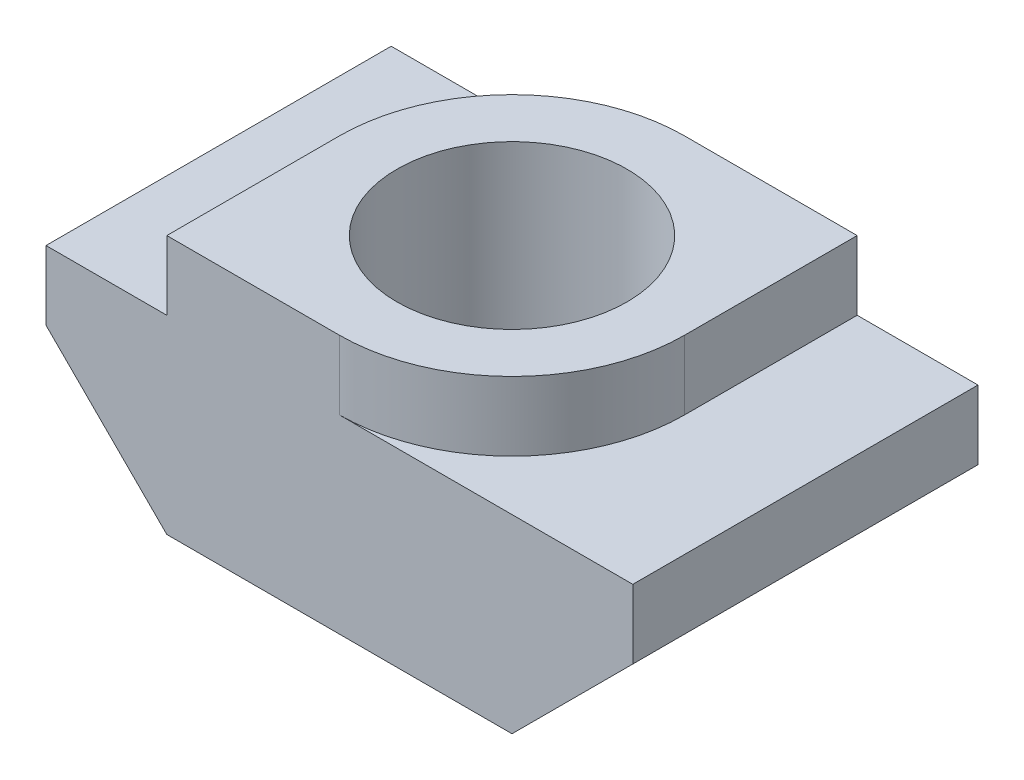
SolidWorks part; units mm, degrees
ref_plane "前视基准面" through (0, 0, 0) normal (0, 0, 1) x (1, 0, 0)
ref_plane "上视基准面" through (0, 0, 0) normal (0, 1, 0) x (1, 0, 0)
ref_plane "右视基准面" through (0, 0, 0) normal (1, 0, 0) x (0, 0, -1)
other "Configuration Table"
sketch "草图1" plane through (0, 0, 0) normal (0, 1, 0) x (1, 0, 0)
  line L1 (0, 0) -> (10.2, 0)
  line L2 (0, 0) -> (0, 6)
  line L3 (0, 6) -> (10.2, 6)
  line L4 (10.2, 0) -> (10.2, 6)
  dimension "D1" = 6
  dimension "D2" = 10.2
extrude "凸台-拉伸1" add sketch "草图1" along normal blind 3.3
sketch "草图2" plane through (0, 0, 0) normal (0, 1, 0) x (1, 0, 0)
  line L0 (10.2, 6) -> (0, 6) construction
  line L1 (2.1, 3) -> (2.1, 0)
  line L2 (0, 0) -> (10.2, 0) construction
  line L3 (2.1, 0) -> (5.1, 0)
  line L4 (5.1, 6) -> (8.1, 6)
  line L5 (8.1, 6) -> (8.1, 3)
  circle A0 centre (5.1, 3) radius 2
  arc A1 (5.1, 0) -> (8.1, 3) centre (5.1, 3) ccw
  arc A2 (5.1, 6) -> (2.1, 3) centre (5.1, 3) ccw
  dimension "D3" = 4
  dimension "D1" = 3
  dimension "D2" = 5.1
extrude "凸台-拉伸2" add sketch "草图2" along normal blind 1.2 from surface contours A1 L5 L4 A2 L1 L3 starting at face at (5.1, 3.3, -3)
sketch "草图3" plane through (0, 0, 0) normal (0, 0, 1) x (1, 0, 0)
  line L0 (0, 2.1) -> (2.1, 0)
  line L1 (0, 3.3) -> (0, 0) construction
  line L2 (0, 0) -> (10.2, 0) construction
  line L3 (2.1, 0) -> (8.1, 0) construction
  line L4 (8.1, 0) -> (10.2, 2.1)
  line L5 (10.2, 3.3) -> (10.2, 0) construction
  line L6 (10.2, 2.1) -> (0, 2.1) construction
  line L7 (0, 3.3) -> (2.1, 3.3) construction
  line L8 (5.1, 9.0744) -> (5.1, -3.0876) construction
  line L9 (0, 2.1) -> (0, 0)
  line L10 (0, 0) -> (2.1, 0)
  line L11 (10.2, 2.1) -> (10.2, 0)
  line L12 (10.2, 0) -> (8.1, 0)
  point P6 (7.8566, 0)
  point P11 (0, 0)
  point P14 (0, 0)
  dimension "D1" = 1.2
  dimension "D2" = 135
extrude "切除-拉伸2" cut sketch "草图3" against normal through all
extrude "切除-拉伸4" cut sketch "草图2<5>" along normal through all contours A0
sketch "草图2<5>" plane through (0, 0, 0) normal (0, 1, 0) x (1, 0, 0) same geometry as "草图2"
